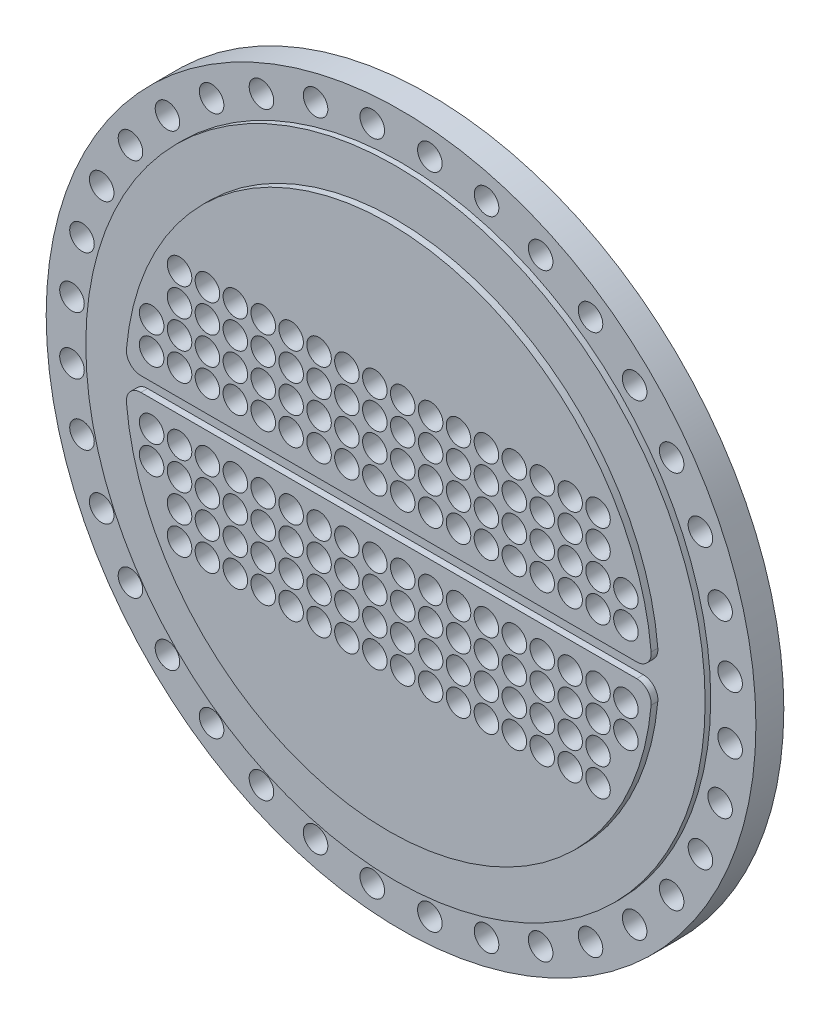
SolidWorks part; units mm, degrees
note: The reader was unsure of these and kept them because the rebuilt part matched: shared geometry of "Sketch1<3>", "Sketch1<4>".
ref_plane "Front Plane" through (0, 0, 0) normal (0, 0, 1) x (1, 0, 0)
ref_plane "Top Plane" through (0, 0, 0) normal (0, 1, 0) x (1, 0, 0)
ref_plane "Right Plane" through (0, 0, 0) normal (1, 0, 0) x (0, 0, -1)
sketch "Sketch1" plane through (0, 0, 0) normal (0, 0, 1) x (1, 0, 0)
  circle A0 centre (0, 0) radius 318
  circle A1 centre (0, 0) radius 236
  circle A2 centre (0, 0) radius 277.5
  dimension "D1" = 636
  dimension "D2" = 472
  dimension "D3" = 555
extrude "Boss-Extrude1" add sketch "Sketch1" along normal mid plane 47 contours A1
extrude "Boss-Extrude2" add sketch "Sketch1<3>" along normal mid plane 25 separate body contours A0 A2
sketch "Sketch1<3>" plane through (0, 0, 0) normal (0, 0, 1) x (1, 0, 0) same geometry as "Sketch1"
extrude "Boss-Extrude3" add sketch "Sketch1<4>" along normal mid plane 35 contours A2 A1
sketch "Sketch1<4>" plane through (0, 0, 0) normal (0, 0, 1) x (1, 0, 0) same geometry as "Sketch1"
sketch "Sketch2" plane through (0, 0, 23.5) normal (0, 0, 1) x (1, 0, 0)
  line L1 (-253.9776, -6.5) -> (253.9776, -6.5)
  line L2 (-253.9776, -6.5) -> (-253.9776, 6.5)
  line L3 (-253.9776, 6.5) -> (253.9776, 6.5)
  line L4 (253.9776, -6.5) -> (253.9776, 6.5)
  line L5 (-253.9776, -6.5) -> (253.9776, 6.5) construction
  line L6 (-253.9776, 6.5) -> (253.9776, -6.5) construction
  point P0 (0, 0)
  dimension "D1" = 13
extrude "Cut-Extrude1" cut sketch "Sketch2" against normal up to surface (6 mm away) up to face at (236, 0, 17.5)
fillet "Fillet1" radius 13 4 edges at (-235.9105, 6.5, 20.5) (235.9105, 6.5, 20.5) (235.9105, -6.5, 20.5) (-235.9105, -6.5, 20.5)
sketch "Sketch3" plane through (0, 0, 12.5) normal (0, 0, 1) x (1, 0, 0)
  line L0 (0, 376.5993) -> (0, -376.5566) construction
  line L1 (0, 0) -> (29.6447, 338.841) construction
  line L2 (0, 0) -> (76.6104, 285.914) construction
  circle A0 centre (0, 0) radius 296 construction
  circle A1 centre (25.7981, 294.8736) radius 11
  circle A2 centre (76.6104, 285.914) radius 11
  circle A3 centre (125.095, 268.2671) radius 11
  circle A4 centre (169.7786, 242.469) radius 11
  circle A5 centre (209.3036, 209.3036) radius 11
  circle A6 centre (242.469, 169.7786) radius 11
  circle A7 centre (268.2671, 125.095) radius 11
  circle A8 centre (285.914, 76.6104) radius 11
  circle A9 centre (294.8736, 25.7981) radius 11
  circle A10 centre (294.8736, -25.7981) radius 11
  circle A11 centre (285.914, -76.6104) radius 11
  circle A12 centre (268.2671, -125.095) radius 11
  circle A13 centre (242.469, -169.7786) radius 11
  circle A14 centre (209.3036, -209.3036) radius 11
  circle A15 centre (169.7786, -242.469) radius 11
  circle A16 centre (125.095, -268.2671) radius 11
  circle A17 centre (76.6104, -285.914) radius 11
  circle A18 centre (25.7981, -294.8736) radius 11
  circle A19 centre (-25.7981, -294.8736) radius 11
  circle A20 centre (-76.6104, -285.914) radius 11
  circle A21 centre (-125.095, -268.2671) radius 11
  circle A22 centre (-169.7786, -242.469) radius 11
  circle A23 centre (-209.3036, -209.3036) radius 11
  circle A24 centre (-242.469, -169.7786) radius 11
  circle A25 centre (-268.2671, -125.095) radius 11
  circle A26 centre (-285.914, -76.6104) radius 11
  circle A27 centre (-294.8736, -25.7981) radius 11
  circle A28 centre (-294.8736, 25.7981) radius 11
  circle A29 centre (-285.914, 76.6104) radius 11
  circle A30 centre (-268.2671, 125.095) radius 11
  circle A31 centre (-242.469, 169.7786) radius 11
  circle A32 centre (-209.3036, 209.3036) radius 11
  circle A33 centre (-169.7786, 242.469) radius 11
  circle A34 centre (-125.095, 268.2671) radius 11
  circle A35 centre (-76.6104, 285.914) radius 11
  circle A36 centre (-25.7981, 294.8736) radius 11
  point P81 (0, 0)
  dimension "D1" = 592
  dimension "D2" = 22
  dimension "D3" = 5
  dimension "D5" = 10
  dimension "D4" = 36
extrude "Cut-Extrude2" cut sketch "Sketch3" against normal through all
sketch "Sketch7" plane through (0, 0, -23.5) normal (0, 0, -1) x (-1, 0, 0)
  circle A0 centre (0, 0) radius 190 construction
  dimension "D1" = 380
hole_wizard "3/8-16 Tapped Hole1" positions "Sketch8" profile "Sketch10" tap size "3/8-16" standard "ANSI Inch"
sketch "Sketch8" plane through (0, 0, -23.5) normal (0, 0, -1) x (-1, 0, 0)
  line L0 (0, 0) -> (0, -360.0291) construction
  line L2 (0, 0) -> (-218.0497, -377.6731) construction
  circle A0 centre (0, 0) radius 190 construction
  point P0 (-95, -164.5448)
  dimension "D1" = 30
sketch "Sketch10" plane through (95, -164.5448, -23.5) normal (1, 0, 0) x (0, 1, 0)
  line L0 (0, 0) -> (0, 34.3847)
  line L1 (0, 34.3847) -> (3.9687, 32)
  line L2 (3.9687, 32) -> (3.9687, 25)
  line L3 (3.9687, 25) -> (4.7625, 25)
  line L4 (4.7625, 25) -> (4.7625, 0)
  line L5 (4.7625, 0) -> (0, 0)
  line L10 (0, 34.3847) -> (-3.9688, 32) construction
  line L11 (0, -6.35) -> (0, 107.95) construction
  dimension "Tap Drill Dia." = 7.9375
  dimension "Tap Drill Depth" = 32
  dimension "Thread Major Dia." = 9.525
  dimension "Thread Depth" = 25
  dimension "Drill Angle" = 118
pattern_circular "CirPattern1" count 6 over 360 about axis through (-0.0387, 0.067, 0) along (0, 0, 1) of "3/8-16 Tapped Hole1"
sketch "Sketch11" plane through (0, 0, 23.5) normal (0, 0, 1) x (1, 0, 0)
  line L0 (-378.6906, 0) -> (438.7713, 0) construction
  line L1 (0, 378.1808) -> (0, -395.2219) construction
  circle A0 centre (12.5, -30) radius 11
  circle A1 centre (12.5, -55) radius 11
  circle A2 centre (12.5, -80) radius 11
  circle A3 centre (12.5, -105) radius 11
  circle A4 centre (37.5, -30) radius 11
  circle A5 centre (37.5, -55) radius 11
  circle A6 centre (62.5, -30) radius 11
  circle A7 centre (62.5, -55) radius 11
  circle A8 centre (87.5, -30) radius 11
  circle A9 centre (87.5, -55) radius 11
  circle A10 centre (112.5, -30) radius 11
  circle A11 centre (112.5, -55) radius 11
  circle A12 centre (137.5, -30) radius 11
  circle A13 centre (137.5, -55) radius 11
  circle A14 centre (162.5, -30) radius 11
  circle A15 centre (162.5, -55) radius 11
  circle A16 centre (187.5, -30) radius 11
  circle A17 centre (187.5, -55) radius 11
  circle A18 centre (212.5, -30) radius 11
  circle A19 centre (212.5, -55) radius 11
  circle A20 centre (37.5, -80) radius 11
  circle A21 centre (37.5, -105) radius 11
  circle A22 centre (62.5, -80) radius 11
  circle A23 centre (62.5, -105) radius 11
  circle A24 centre (87.5, -80) radius 11
  circle A25 centre (87.5, -105) radius 11
  circle A26 centre (112.5, -80) radius 11
  circle A27 centre (112.5, -105) radius 11
  circle A28 centre (137.5, -80) radius 11
  circle A29 centre (137.5, -105) radius 11
  circle A30 centre (162.5, -80) radius 11
  circle A31 centre (162.5, -105) radius 11
  circle A32 centre (187.5, -80) radius 11
  circle A33 centre (187.5, -105) radius 11
  dimension "D1" = 22
  dimension "D2" = 22
  dimension "D6" = 22
  dimension "D7" = 22
  dimension "D3" = 30
  dimension "D4" = 55
  dimension "D5" = 12.5
  dimension "D8" = 80
  dimension "D9" = 105
  dimension "D12" = 37.5
  dimension "D13" = 37.5
  dimension "D10" = 9
  dimension "D11" = 8
extrude "Cut-Extrude3" cut sketch "Sketch11" against normal through all
mirror "Mirror1" about plane through (0, 0, 0) normal (0, 1, 0) of "Cut-Extrude3" second plane through (0, 0, 0) second plane normal (1, 0, 0)
